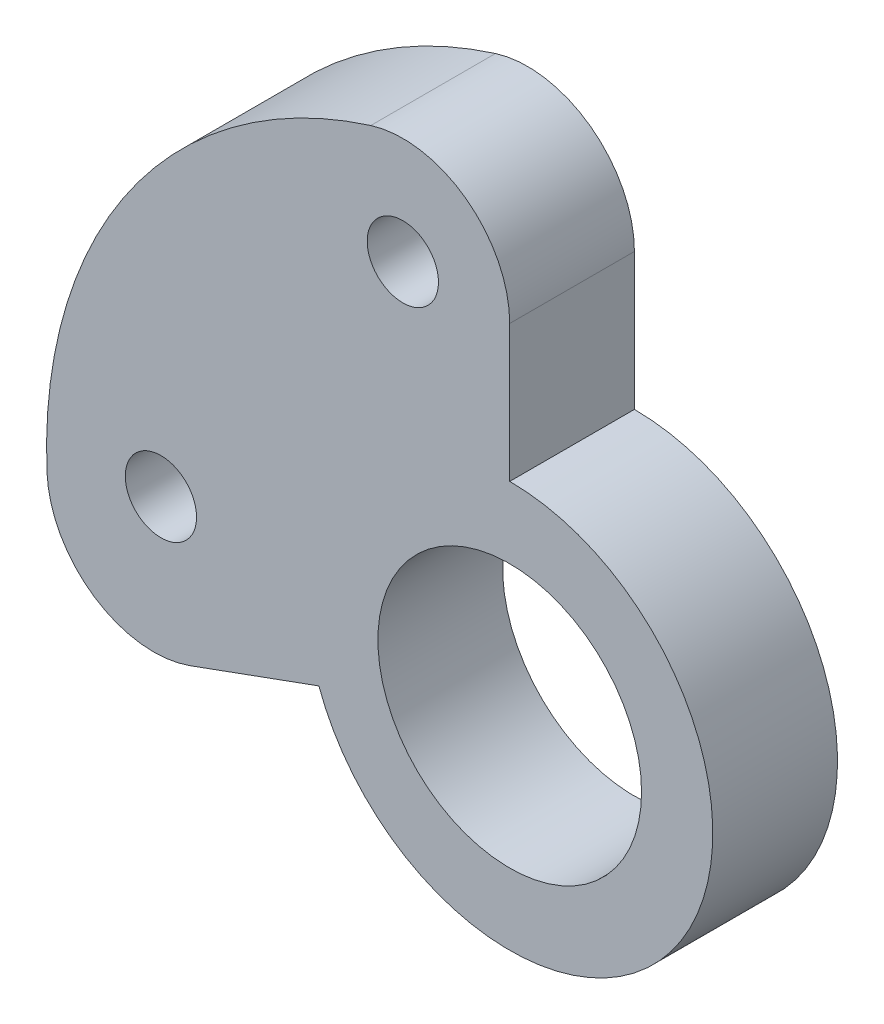
SolidWorks part; units mm, degrees
ref_plane "Front Plane" through (0, 0, 0) normal (0, 0, 1) x (1, 0, 0)
ref_plane "Top Plane" through (0, 0, 0) normal (0, 1, 0) x (1, 0, 0)
ref_plane "Right Plane" through (0, 0, 0) normal (1, 0, 0) x (0, 0, -1)
sketch "Sketch1" plane through (0, 0, 0) normal (0, 0, 1) x (1, 0, 0)
  circle A0 centre (0, 0) radius 3.7
  circle A1 centre (0, 0) radius 5.7
  circle A2 centre (0, 0) radius 13
  dimension "D1" = 7.4
  dimension "D2" = 2
  dimension "D3" = 26
extrude "Boss-Extrude1" add sketch "Sketch1" along normal blind 3.5 contours A1 A0 | A2 A1 region at (-5.5388, 0, 0) region at (-12.6323, 0, 0)
sketch "Sketch2" plane through (0, 0, 3.5) normal (0, 0, 1) x (1, 0, 0)
  line L0 (0, 0) -> (-12.216, -4.4463)
  line L1 (0, 0) -> (0, 13)
  circle A2 centre (0, 0) radius 13
  circle A3 centre (0, 0) radius 13
  circle A4 centre (0, 0) radius 13
  circle A5 centre (0, 0) radius 5.7
  circle A6 centre (0, 0) radius 5.7
  circle A7 centre (0, 0) radius 3.7
  circle A8 centre (0, 0) radius 3.7
  circle M9 centre (0, 0) radius 13
  dimension "D5" = 250
  dimension "D2" = 0
  dimension "D3" = 0
  dimension "D4" = 0
extrude "Cut-Extrude1" cut sketch "Sketch2" against normal blind 10 contours A6 L0 L1 M9 region at (1.0527, -5.9701, 3.5)
sketch "Sketch3" plane through (0, 0, 3.5) normal (0, 0, 1) x (1, 0, 0)
  line L0 (0, 5.7) -> (0, 13) construction
  circle A0 centre (-3, 9.5394) radius 1
  dimension "D1" = 2
  dimension "D3" = 3
  dimension "D2" = 10
extrude "Cut-Extrude2" cut sketch "Sketch3" against normal blind 10
sketch "Sketch5" plane through (0, 0, 3.5) normal (0, 0, 1) x (1, 0, 0)
  line L0 (-3, 9.5394) -> (0, 0) construction
  line L1 (0, 0) -> (-9.7904, 0.4347) construction
  circle A0 centre (-9.7904, 0.4347) radius 1
  circle A1 centre (-3, 9.5394) radius 1 construction
  circle A2 centre (-3, 9.5394) radius 1 construction
  dimension "D2" = 2
  dimension "D3" = 70
  dimension "D1" = 9.8
extrude "Cut-Extrude3" cut sketch "Sketch5" against normal blind 6
fillet "Fillet1" radius 3 2 edges at (-12.216, -4.4463, 1.75) (0, 13, 1.75)
sketch "Sketch6" plane through (0, 0, 0) normal (0, 0, -1) x (-1, 0, 0)
  circle A0 centre (9.7904, 0.4347) radius 2
  circle A1 centre (3, 9.5394) radius 2
  circle A2 centre (9.7904, 0.4347) radius 1 construction
  circle A3 centre (3, 9.5394) radius 1 construction
  circle A4 centre (9.7904, 0.4347) radius 1
  circle A5 centre (3, 9.5394) radius 1
  circle M4 centre (9.7904, 0.4347) radius 1
  circle M5 centre (3, 9.5394) radius 1
  dimension "D1" = 4
extrude "Boss-Extrude2" add sketch "Sketch6" along normal blind 2 contours A0 M4 region at (-7.8469, 0.4347, 0)
extrude "Boss-Extrude3" add sketch "Sketch6<3>" along normal blind 0.5 contours A1 M5 region at (-1.0566, 9.5394, 0)
sketch "Sketch6<3>" plane through (0, 0, 0) normal (0, 0, -1) x (-1, 0, 0) same geometry as "Sketch6"
